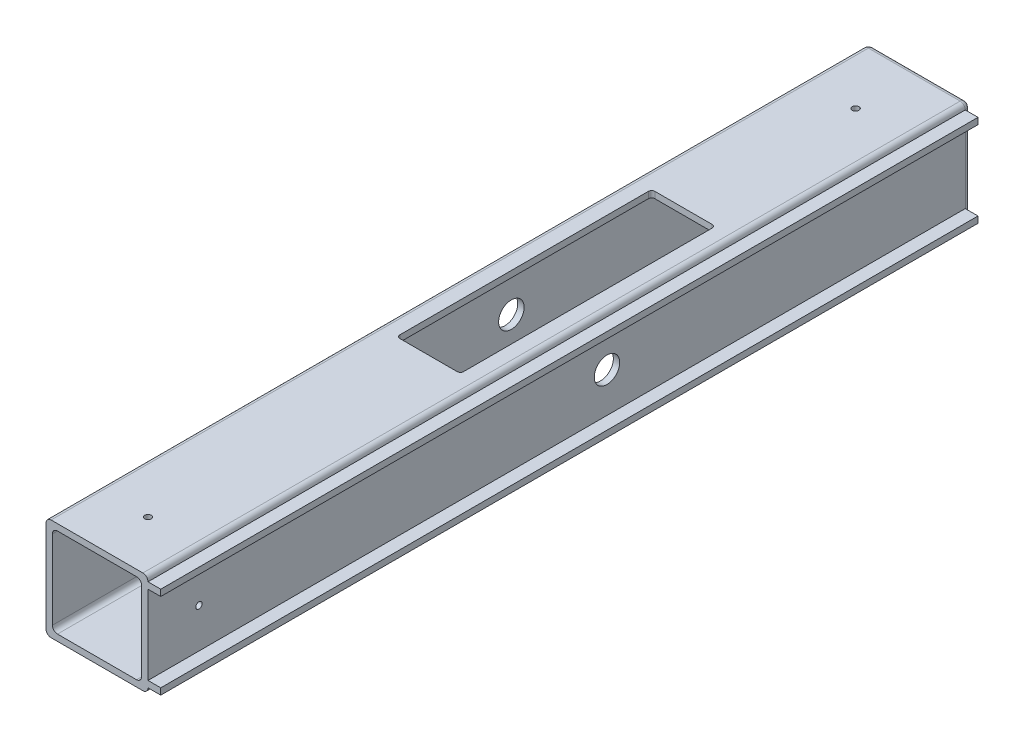
SolidWorks part; units mm, degrees
material "1060 Alloy"
ref_plane "Front Plane" through (0, 0, 0) normal (0, 0, 1) x (1, 0, 0)
ref_plane "Top Plane" through (0, 0, 0) normal (0, 1, 0) x (1, 0, 0)
ref_plane "Right Plane" through (0, 0, 0) normal (1, 0, 0) x (0, 0, -1)
sketch "Sketch1" plane through (0, 0, 0) normal (0, 0, 1) x (1, 0, 0)
  line L0 (3.175, 3.175) -> (3.175, 47.625)
  line L1 (0, 0) -> (50.8, 0)
  line L2 (0, 0) -> (0, 50.8)
  line L3 (0, 50.8) -> (50.8, 50.8)
  line L4 (50.8, 0) -> (50.8, 50.8)
  line L5 (3.175, 47.625) -> (47.625, 47.625)
  line L6 (47.625, 3.175) -> (47.625, 47.625)
  line L7 (3.175, 3.175) -> (47.625, 3.175)
  line L8 (12.7, 12.7) -> (12.7, 38.1)
  line L9 (12.7, 38.1) -> (38.1, 38.1)
  line L10 (38.1, 12.7) -> (38.1, 38.1)
  line L11 (12.7, 12.7) -> (38.1, 12.7)
  line L12 (15.875, 15.875) -> (15.875, 34.925)
  line L13 (15.875, 34.925) -> (34.925, 34.925)
  line L14 (34.925, 15.875) -> (34.925, 34.925)
  line L15 (15.875, 15.875) -> (34.925, 15.875)
  dimension "D3" = 50.8
  dimension "D4" = 50.8
  dimension "D1" = 3.175
  dimension "D2" = 12.7
extrude "Boss-Extrude1" add sketch "Sketch1" along normal blind 406.4 and the other way blind 3.175 contours L1 L4 L3 L2 L7 L0 L5 L6 region at (0.7184, 25.4, 0)
extrude "Boss-Extrude2" add sketch "Sketch1<3>" against normal blind 3.175 contours L0 L7 L6 L5 L11 L8 L9 L10 region at (3.8036, 25.4, 0)
sketch "Sketch1<3>" plane through (0, 0, 0) normal (0, 0, 1) x (1, 0, 0) same geometry as "Sketch1"
extrude "Boss-Extrude3" add sketch "Sketch1<4>" against normal blind 3.175 contours L8 L11 L10 L9 L15 L12 L13 L14 | L12 L13 L14 L15 region at (13.0592, 25.4, 0)
sketch "Sketch1<4>" plane through (0, 0, 0) normal (0, 0, 1) x (1, 0, 0) same geometry as "Sketch1"
sketch "Sketch4" plane through (0, 50.8, 0) normal (0, 1, 0) x (1, 0, 0)
  line L0 (0, -381) -> (50.8, -381) construction
  line L1 (0, 3.175) -> (0, -406.4) construction
  line L2 (50.8, 3.175) -> (50.8, -406.4) construction
  line L3 (0, -406.4) -> (50.8, -406.4) construction
  line L4 (0, 3.175) -> (50.8, 3.175) construction
  line L5 (9.525, -241.3) -> (41.275, -241.3)
  line L6 (9.525, -241.3) -> (9.525, -114.3)
  line L7 (9.525, -114.3) -> (41.275, -114.3)
  line L8 (41.275, -241.3) -> (41.275, -114.3)
  line L9 (9.525, -241.3) -> (41.275, -114.3) construction
  line L10 (9.525, -114.3) -> (41.275, -241.3) construction
  circle A0 centre (25.4, -381) radius 1.5875
  circle A1 centre (25.4, -28.575) radius 1.651
  point P10 (25.4, -177.8)
  dimension "D1" = 3.175
  dimension "D6" = 3.302
  dimension "D2" = 25.4
  dimension "D3" = 203.2
  dimension "D4" = 31.75
  dimension "D5" = 127
  dimension "D7" = 31.75
extrude "Cut-Extrude3" cut sketch "Sketch4" against normal up to surface (50.8 mm away) up to face at (25.4, 0, 201.6125)
sketch "Sketch5" plane through (50.8, 0, 0) normal (1, 0, 0) x (0, 0, -1)
  line L0 (-381, 50.8) -> (-381, 0) construction
  line L2 (3.175, 50.8) -> (-406.4, 50.8) construction
  line L3 (3.175, 0) -> (-406.4, 0) construction
  line L4 (-406.4, 0) -> (-406.4, 50.8) construction
  circle A1 centre (-381, 25.4) radius 1.5875
  circle A2 centre (-177.8, 25.4) radius 6.35
  dimension "D1" = 3.175
  dimension "D2" = 25.4
  dimension "D3" = 203.2
  dimension "D4" = 12.7
extrude "Cut-Extrude4" cut sketch "Sketch5" against normal up to surface (50.8 mm away) contours A1 | A2 up to face at (0, 25.4, 201.6125)
fillet "Fillet1" radius 2.54 8 edges at (25.4, 50.8, -3.175) (50.8, 25.4, -3.175) (50.8, 50.8, 201.6125) (25.4, 0, -3.175) (50.8, 0, 201.6125) (0, 25.4, -3.175) (0, 50.8, 201.6125) (0, 0, 201.6125)
fillet "Fillet4" radius 2.54 4 edges at (3.175, 3.175, 203.2) (47.625, 3.175, 203.2) (47.625, 47.625, 203.2) (3.175, 47.625, 203.2)
sketch "Sketch7" plane through (50.8, 0, 0) normal (1, 0, 0) x (0, 0, -1)
  line L0 (-406.4, 2.54) -> (-406.4, 48.26) construction
  line L1 (0.635, 48.26) -> (-406.4, 48.26)
  line L2 (0.635, 48.26) -> (0.635, 45.085)
  line L3 (0.635, 45.085) -> (-406.4, 45.085)
  line L4 (-406.4, 48.26) -> (-406.4, 45.085)
  line L6 (0.635, 2.54) -> (-406.4, 2.54)
  line L7 (0.635, 2.54) -> (0.635, 5.715)
  line L8 (0.635, 5.715) -> (-406.4, 5.715)
  line L9 (-406.4, 2.54) -> (-406.4, 5.715)
  dimension "D1" = 3.175
  dimension "D2" = 3.175
extrude "Boss-Extrude4" add sketch "Sketch7" along normal blind 6.35
fillet "Fillet5" radius 1.5875 8 edges at (9.525, 49.2125, 114.3) (41.275, 49.2125, 114.3) (41.275, 1.5875, 114.3) (9.525, 1.5875, 114.3) (41.275, 49.2125, 241.3) (9.525, 49.2125, 241.3) (9.525, 1.5875, 241.3) (41.275, 1.5875, 241.3)
equation "\"sheet_thickness\"= 1 / 8in'Universal thickness of a metal sheet"
equation "\"offset_visible_hidden\"= 0.5in'The distance between the outter and inner shell"
equation "\"hole_size_STD\"= 1 / 8in'Standard hole size"
equation "\"fillet_radius\"= 1 / 16in'Standard fillet radius"
equation "\"D1@Sketch1\"=\"sheet_thickness\""
equation "\"visible_side\"= 2in'The side of a square bracket"
equation "\"D3@Sketch1\"=\"visible_side\""
equation "\"D4@Sketch1\"=\"visible_side\""
equation "\"D2@Sketch1\"=\"offset_visible_hidden\""
equation "\"D5@Sketch1\"=\"sheet_thickness\""
equation "\"visible_length\"= 12in'The length of the visible bar"
equation "\"hidden_length\"= 2in'The length of the hidden bar"
equation "\"D1@Boss-Extrude1\"=\"visible_length\"+4"
equation "\"D2@Boss-Extrude1\"=\"sheet_thickness\""
equation "\"D1@Boss-Extrude2\"=\"sheet_thickness\""
equation "\"D1@Boss-Extrude3\"=\"sheet_thickness\""
equation "\"D1@Sketch4\"=\"hole_size_STD\""
equation "\"D2@Sketch5\"=\"hidden_length\"/2in"
equation "\"D1@Sketch5\"=\"hole_size_STD\""
equation "\"D1@Fillet5\"=\"fillet_radius\""
